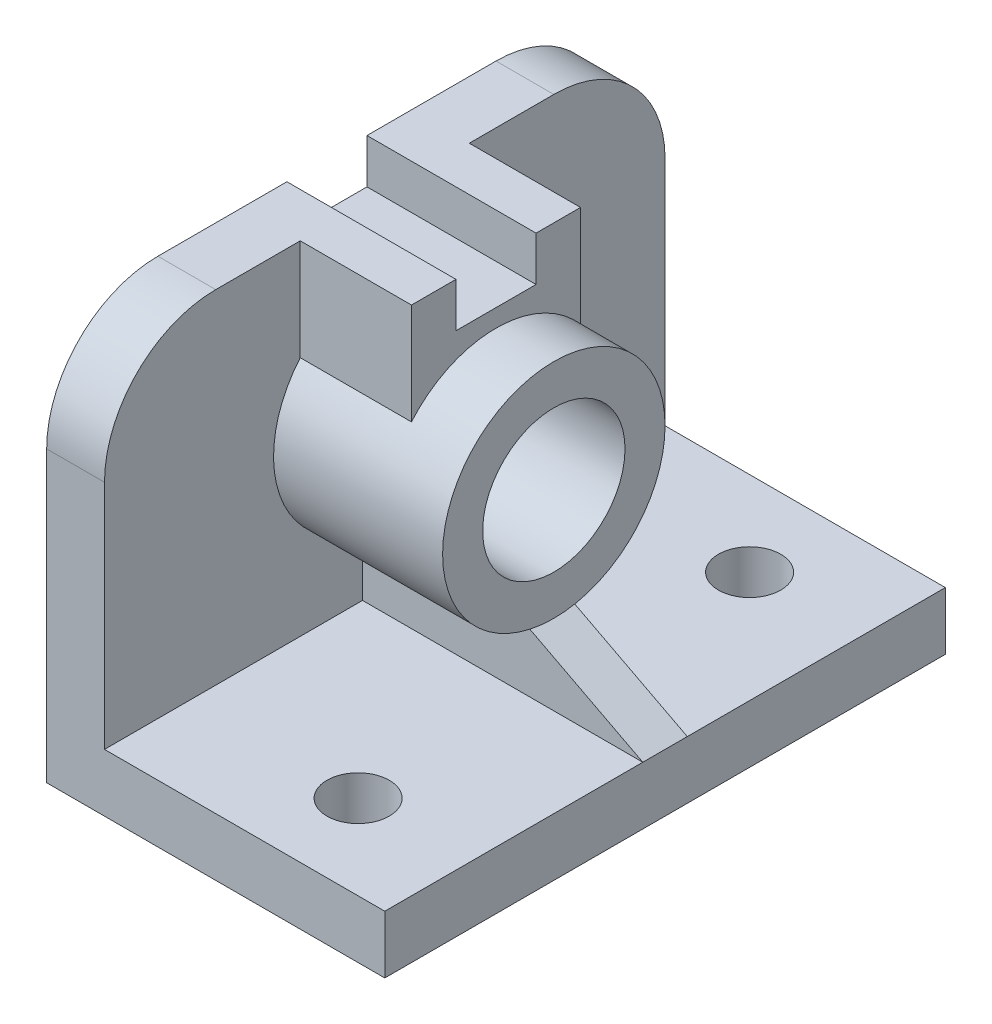
SolidWorks part; units mm, degrees
material "1060 Alloy"
ref_plane "Front Plane" through (0, 0, 0) normal (0, 0, 1) x (1, 0, 0)
ref_plane "Top Plane" through (0, 0, 0) normal (0, 1, 0) x (1, 0, 0)
ref_plane "Right Plane" through (0, 0, 0) normal (1, 0, 0) x (0, 0, -1)
sketch "Sketch1" plane through (0, 0, 0) normal (0, 1, 0) x (1, 0, 0)
  line L1 (38, -63) -> (-38, -63)
  line L2 (38, -63) -> (38, 63)
  line L3 (38, 63) -> (-38, 63)
  line L4 (-38, -63) -> (-38, 63)
  line L5 (38, -63) -> (-38, 63) construction
  line L6 (38, 63) -> (-38, -63) construction
  point P0 (0, 0)
  dimension "D1" = 126
  dimension "D2" = 76
extrude "Boss-Extrude1" add sketch "Sketch1" along normal blind 13 contours L3 L4 L1 L2
sketch "Sketch2" plane through (0, 13, 0) normal (0, 1, 0) x (1, 0, 0)
  line L1 (-38, -63) -> (-38, 63)
  line L2 (-38, -63) -> (-25, -63)
  line L3 (-25, -63) -> (-25, 63)
  line L4 (-38, 63) -> (-25, 63)
  line L5 (38, -63) -> (-38, -63) construction
  line L6 (38, 63) -> (-38, 63) construction
  point P5 (10.2072, 29.3766)
  point P6 (-21.7315, -63)
  point P7 (-38, -63)
  point P9 (38, -76)
  point P12 (-24.9254, 59.186)
  point P13 (-16.8342, 64.5091)
  point P14 (-38, 63)
  point P16 (-17.6859, 63)
  dimension "D1" = 13
extrude "Boss-Extrude2" add sketch "Sketch2" along normal blind 77
fillet "Fillet1" radius 25 2 edges at (-31.5, 90, -63) (-31.5, 90, 63)
sketch "Sketch3" plane through (-25, 0, 0) normal (1, 0, 0) x (0, 0, -1)
  line L0 (-38, 90) -> (38, 90) construction
  line L1 (-9, 90) -> (9, 90)
  line L2 (-9, 90) -> (-9, 80)
  line L3 (-9, 80) -> (9, 80)
  line L4 (9, 90) -> (9, 80)
  line L5 (-19, 90) -> (-19, 67.2481)
  line L7 (19, 67.2481) -> (19, 90)
  line L8 (-19, 90) -> (-9, 90)
  line L9 (9, 90) -> (19, 90)
  line L10 (-63, 13) -> (63, 13) construction
  circle A0 centre (0, 51) radius 25
  circle A1 centre (0, 51) radius 16
  point P6 (0, 90)
  point P17 (0, 0)
  line M11 (38, 90) -> (-38, 90)
  dimension "D5" = 50
  dimension "D6" = 32
  dimension "D1" = 18
  dimension "D2" = 10
  dimension "D3" = 10
  dimension "D4" = 10
  dimension "D7" = 38
extrude "Cut-Extrude1" cut sketch "Sketch3" against normal through all contours L4 L2 L3 M11 region at (-25, 85, 0)
extrude "Boss-Extrude3" add sketch "Sketch3<3>" along normal blind 25 contours A0 L7 L4 L3 L2 L5 M11 region at (-25, 85, 9.4429)
sketch "Sketch3<3>" plane through (-25, 0, 0) normal (1, 0, 0) x (0, 0, -1) same geometry as "Sketch3"
extrude "Boss-Extrude4" add sketch "Sketch3<4>" along normal blind 38 contours A0 A1 region at (-25, 75.2929, 0)
sketch "Sketch3<4>" plane through (-25, 0, 0) normal (1, 0, 0) x (0, 0, -1) same geometry as "Sketch3"
sketch "Sketch4" plane through (0, 0, 0) normal (0, 0, 1) x (1, 0, 0)
  line L0 (13, 26) -> (38, 13)
  line L1 (13, 26) -> (13, 76) construction
  line L2 (-25, 26) -> (13, 26) construction
  point P5 (13, 27.9348)
rib "Rib1" sketch "Sketch4" sketch "Sketch4" thickness 10 extrusion direction parallel to sketch draft on no parameters "D1"=10
sketch "Sketch5" plane through (0, 13, 0) normal (0, 1, 0) x (1, 0, 0)
  line L0 (38, -63) -> (-25, -63) construction
  line L1 (38, -63) -> (38, -5) construction
  line L2 (-41.8, 0) -> (41.8, 0) construction
  circle A0 centre (13, -44) radius 7
  circle A1 centre (13, 44) radius 7
  dimension "D1" = 14
  dimension "D2" = 19
  dimension "D3" = 25
extrude "Cut-Extrude2" cut sketch "Sketch5" against normal through all
extrude "Cut-Extrude3" cut sketch "Sketch3<5>" against normal through all contours A1
sketch "Sketch3<5>" plane through (-25, 0, 0) normal (1, 0, 0) x (0, 0, -1) same geometry as "Sketch3"
